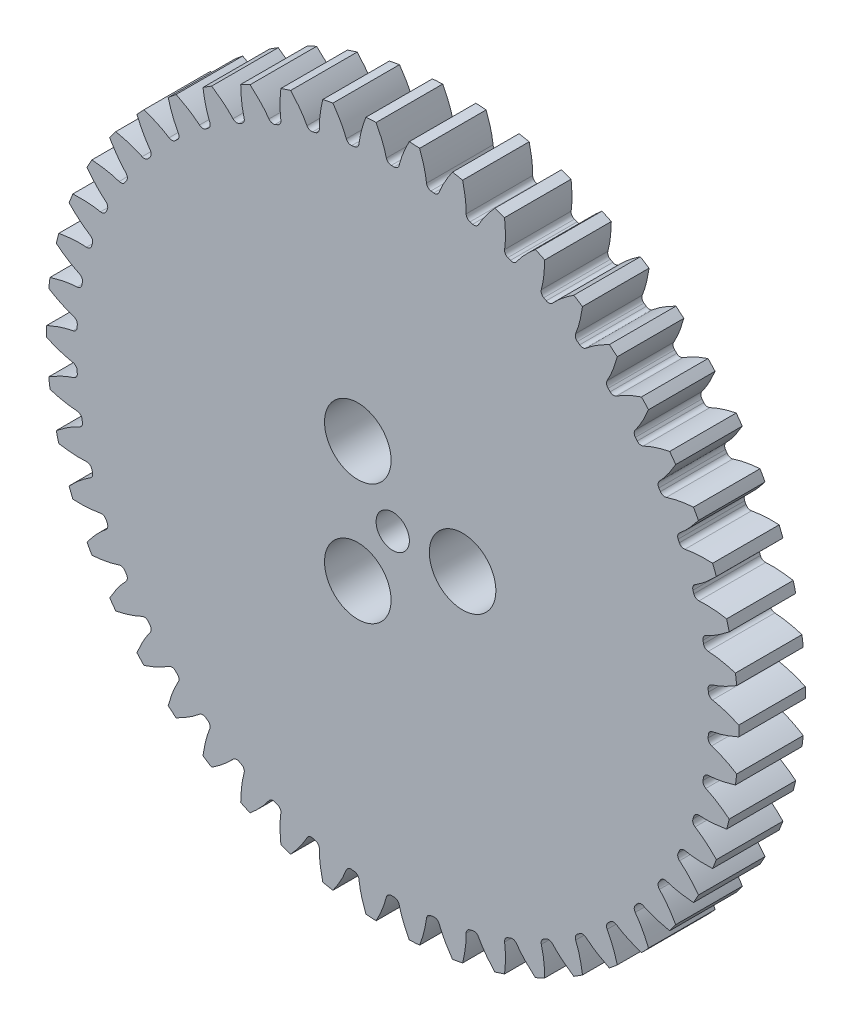
SolidWorks part; units mm, degrees
ref_plane "前视基准面" through (0, 0, 0) normal (0, 0, 1) x (1, 0, 0)
ref_plane "上视基准面" through (0, 0, 0) normal (0, 1, 0) x (1, 0, 0)
ref_plane "右视基准面" through (0, 0, 0) normal (1, 0, 0) x (0, 0, -1)
other "Configuration Table"
ref_axis "Axis1" through (0, 0, -88.99) along (0, 0, 1)
sketch "草图1" plane through (0, 0, 0) normal (0, 0, 1) x (1, 0, 0)
  circle A0 centre (0, 0) radius 52
extrude "LaShenA" add sketch "草图1" along normal blind 10
sketch "SketchA" plane through (0, 0, 10) normal (0, 0, 1) x (1, 0, 0)
  line L0 (0, 0) -> (0, 52) construction
  arc A0 (0.2136, 47.4995) -> (-0.2136, 47.4995) centre (0, 0) ccw
  arc A1 (3.108, 53.0234) -> (-3.108, 53.0234) centre (0, 0) ccw
  arc A2 (-0.2136, 47.4995) -> (-0.9549, 48.0774) centre (-0.217, 48.2595) cw
  arc A3 (0.9549, 48.0774) -> (0.2136, 47.4995) centre (0.217, 48.2595) cw
  circle A4 centre (0, 0) radius 46.9846 construction
  circle A5 centre (0, 0) radius 52 construction
  circle A6 centre (0, 0) radius 47.5 construction
  circle A7 centre (0, 0) radius 50 construction
  spline S0 degree 3 poles (0.9549, 48.0774) (0.9654, 48.1201) (0.9855, 48.2008) (1.0164, 48.321) (1.0483, 48.4395) (1.0828, 48.5627) (1.1202, 48.6905) (1.1604, 48.8231) (1.2037, 48.9602) (1.25, 49.1019) (1.2995, 49.2481) (1.3523, 49.3988) (1.4085, 49.5538) (1.4681, 49.7132) (1.5314, 49.8768) (1.5984, 50.0447) (1.6691, 50.2168) (1.7437, 50.3929) (1.8223, 50.5731) (1.905, 50.7573) (1.9918, 50.9453) (2.0829, 51.1372) (2.1783, 51.3329) (2.2782, 51.5323) (2.3825, 51.7353) (2.4915, 51.9418) (2.6052, 52.1519) (2.7236, 52.3653) (2.8898, 52.6574) (3.0193, 52.8767) (3.108, 53.0234) knots 0.100221 0.100221 0.100221 0.100221 0.122181 0.141688 0.162073 0.183335 0.205475 0.228491 0.252385 0.277157 0.302805 0.329331 0.356734 0.385014 0.414171 0.444206 0.475118 0.506908 0.539574 0.573118 0.607539 0.642838 0.679013 0.716066 0.753996 0.792804 0.832488 0.87305 0.91449 1 1 1 1
  spline S1 degree 3 poles (-0.9549, 48.0774) (-0.9654, 48.1201) (-0.9855, 48.2008) (-1.0164, 48.321) (-1.0483, 48.4395) (-1.0828, 48.5627) (-1.1202, 48.6905) (-1.1604, 48.8231) (-1.2037, 48.9602) (-1.25, 49.1019) (-1.2995, 49.2481) (-1.3523, 49.3988) (-1.4085, 49.5538) (-1.4681, 49.7132) (-1.5314, 49.8768) (-1.5984, 50.0447) (-1.6691, 50.2168) (-1.7437, 50.3929) (-1.8223, 50.5731) (-1.905, 50.7573) (-1.9918, 50.9453) (-2.0829, 51.1372) (-2.1783, 51.3329) (-2.2782, 51.5323) (-2.3825, 51.7353) (-2.4915, 51.9418) (-2.6052, 52.1519) (-2.7236, 52.3653) (-2.8898, 52.6574) (-3.0193, 52.8767) (-3.108, 53.0234) knots 0.100221 0.100221 0.100221 0.100221 0.122181 0.141688 0.162073 0.183335 0.205475 0.228491 0.252385 0.277157 0.302805 0.329331 0.356734 0.385014 0.414171 0.444206 0.475118 0.506908 0.539574 0.573118 0.607539 0.642838 0.679013 0.716066 0.753996 0.792804 0.832488 0.87305 0.91449 1 1 1 1
  dimension "D1" = 0.76
  dimension "Db" = 93.9693
  dimension "Da" = 104
  dimension "Df" = 95
  dimension "Dn" = 100
extrude "Cut-ExtrudeA" cut sketch "SketchA" against normal blind 10
pattern_circular "www.KYTool.cn" count 50 over 360 about axis through (0, 0, -88.99) along (0, 0, 1) of "Cut-ExtrudeA"
ref_plane "基准面1" through (0, 0, 10) normal (0, 0, 1) x (1, 0, 0)
sketch "草图3" plane through (0, 0, 10) normal (0, 0, 1) x (1, 0, 0)
  circle A0 centre (0, 0) radius 2.5
  dimension "D1" = 5
extrude "切除-拉伸2" cut sketch "草图3" against normal up to next
sketch "草图4" plane through (0, 0, 10) normal (0, 0, 1) x (1, 0, 0)
  line L0 (0, 0) -> (52, 0) construction
  line L1 (10.5, 0) -> (10.5, 21.3539) construction
  arc A0 (51.9942, -0.7751) -> (51.9942, 0.7751) centre (0, 0) ccw construction
  circle A1 centre (10.5, 0) radius 5
  dimension "D2" = 10
  dimension "D1" = 10.5
extrude "切除-拉伸3" cut sketch "草图4" against normal up to next
pattern_circular "阵列(圆周)1" count 3 over 360 about axis through (0, 0, -0.001) along (0, 0, 1) of "切除-拉伸3"
